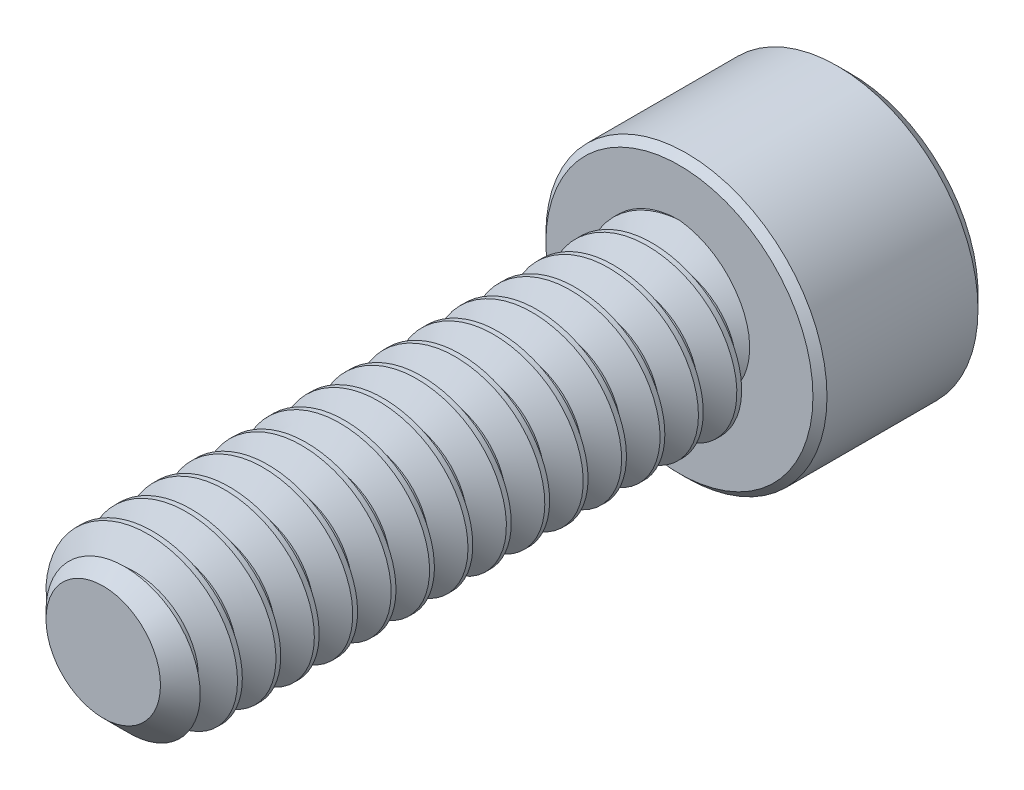
SolidWorks part; units mm, degrees
ref_plane "Front Plane" through (0, 0, 0) normal (0, 0, 1) x (1, 0, 0)
ref_plane "Top Plane" through (0, 0, 0) normal (0, 1, 0) x (1, 0, 0)
ref_plane "Right Plane" through (0, 0, 0) normal (1, 0, 0) x (0, 0, -1)
sketch "Sketch0" plane through (0, 0, 0) normal (1, 0, 0) x (0, 0, -1)
  line L0 (0, 0) -> (9.525, 0) construction
  point P2 (12.3698, 0)
  point P4 (0, 0)
  dimension "D1" = 9.525
  dimension "D2" = 2.8448
  dimension "Min Thread" = 0
sketch "Sketch1" plane through (0, 0, 0) normal (0, 0, 1) x (1, 0, 0)
  circle A0 centre (0, 0) radius 1.4224
  dimension "OD" = 2.8448
extrude "Extrude1" add sketch "Sketch1" against normal blind 9.525
sketch "Sketch2" plane through (0, 0, 0) normal (0, 0, 1) x (1, 0, 0)
  circle A0 centre (0, 0) radius 1.4224 construction
  circle A1 centre (0, 0) radius 1.4224
curve "Helix/Spiral1" pitch 0.635 height 10.16 radius 1.4224 centre (0, 0, 0) axis (0, 0, -1) start towards (0, 1, 0) parameters "pitch"=0.635
chamfer "Chamfer3" distance 0.4763 angle 45 1 edges at (1.4224, 0, 0)
sketch "Sketch3" plane through (0, 0, 0) normal (1, 0, 0) x (0, 0, -1)
  line L0 (-0.5556, 1.4224) -> (-0.3175, 1.01)
  line L1 (-0.3175, 1.01) -> (-0.2381, 1.01)
  line L2 (-0.2381, 1.01) -> (0, 1.4224)
  line L3 (-0.5556, 1.4224) -> (0, 1.4224)
  line L4 (-0.2778, 1.4224) -> (-0.2778, 1.01) construction
  line L5 (-0.4366, 1.2162) -> (-0.1191, 1.2162) construction
  line L6 (0, 1.4224) -> (0, -1.4224) construction
  dimension "D1" = 0.0794
  dimension "D2" = 0.3175
  dimension "D3" = 60
sweep "Cut-Sweep1" cut profiles "Sketch3" path "Helix/Spiral1" align with end faces yes
sketch "Sketch5" plane through (0, 0, 0) normal (1, 0, 0) x (0, 0, -1)
  line L0 (9.525, -1.0232) -> (9.525, 1.0149) construction
  line L1 (9.525, 1.4224) -> (0, 1.4224)
  line L2 (9.525, 1.4224) -> (9.525, 0)
  line L3 (9.525, 0) -> (-0.5177, 0)
  line L4 (0, 0) -> (9.525, 0) construction
  line L5 (0, 1.4224) -> (-0.5177, 0)
  line L6 (0, 0) -> (12.065, 0) construction
  dimension "D1" = 70
  dimension "D3" = 2.54
revolve "partially thread" [suppressed] add sketch "Sketch5" angle 360 about L6
sketch "Sketch6" plane through (0, 0, -9.525) normal (0, 0, -1) x (-1, 0, 0)
  circle A0 centre (0, 0) radius 2.3241
  dimension "head dia" = 4.6482
extrude "Extrude2" add sketch "Sketch6" along normal blind 2.8448
sketch "Sketch7" plane through (0, 0, -12.3698) normal (0, 0, -1) x (-1, 0, 0)
  line L1 (0, 1.3748) -> (-1.1906, 0.6874)
  line L2 (-1.1906, 0.6874) -> (-1.1906, -0.6874)
  line L3 (-1.1906, -0.6874) -> (0, -1.3748)
  line L4 (0, -1.3748) -> (1.1906, -0.6874)
  line L5 (1.1906, -0.6874) -> (1.1906, 0.6874)
  line L6 (1.1906, 0.6874) -> (0, 1.3748)
  circle A0 centre (0, 0) radius 1.1906 construction
  dimension "hex dia" = 2.3813
extrude "Cut-Extrude1" cut sketch "Sketch7" against normal blind 1.7859
sketch "Sketch8" plane through (0, 0, -12.3698) normal (0, 0, -1) x (-1, 0, 0)
  circle A0 centre (0, 0) radius 1.3748
extrude "Cut-Extrude2" cut sketch "Sketch8" against normal through all draft 45
chamfer "Chamfer1" distance 0.2324 angle 45 1 edges at (-2.3241, 0, -12.3698)
chamfer "Chamfer2" distance 0.1162 angle 45 1 edges at (-2.3241, 0, -9.525)
sketch "Sketch9" plane through (0, 0, 0) normal (1, 0, 0) x (0, 0, -1)
  line L0 (0, 1.4224) -> (0, -1.4224) construction
  line L1 (1.5875, 1.4224) -> (1.5875, -1.4224) construction
  line L2 (12.3698, 2.3241) -> (12.3698, -2.3241) construction
  line L3 (9.525, 2.3241) -> (9.525, -2.3241) construction
  line L4 (9.525, 2.2079) -> (9.525, -2.2079) construction
  line L5 (12.3698, -2.0917) -> (12.3698, 2.0917) construction
  line L6 (9.525, -2.3241) -> (9.525, 2.3241) construction
  line L7 (0, 0.9462) -> (0, -0.9462) construction
  line L8 (-0.5556, 1.4224) -> (0, 1.4224) construction
  line L9 (1.5875, 0) -> (0, 0) construction
  dimension "D1" = 1.5875
equation "\"D3@Helix/Spiral1\" = \"screw length@Extrude1\"+\"pitch@Helix/Spiral1\""
equation "\"D1@Sketch3\" = \"pitch@Helix/Spiral1\"*.125"
equation "\"D2@Sketch3\" = \"pitch@Helix/Spiral1\"*.5"
equation "\"D1@Cut-Extrude1\" = \"hex dia@Sketch7\"*.75"
equation "\"D1@Chamfer1\" = \"head dia@Sketch6\"*.05"
equation "\"D1@Sketch9\" = \"pitch@Helix/Spiral1\"*2.50"
equation "\"D1@Chamfer2\" = \"D1@Chamfer1\"/2"
equation "\"D1@Chamfer3\" = \"pitch@Helix/Spiral1\"*.750"
equation "\"D1@Sketch0\" = \"screw length@Extrude1\""
equation "\"D2@Sketch0\" = \"head depth@Extrude2\""
